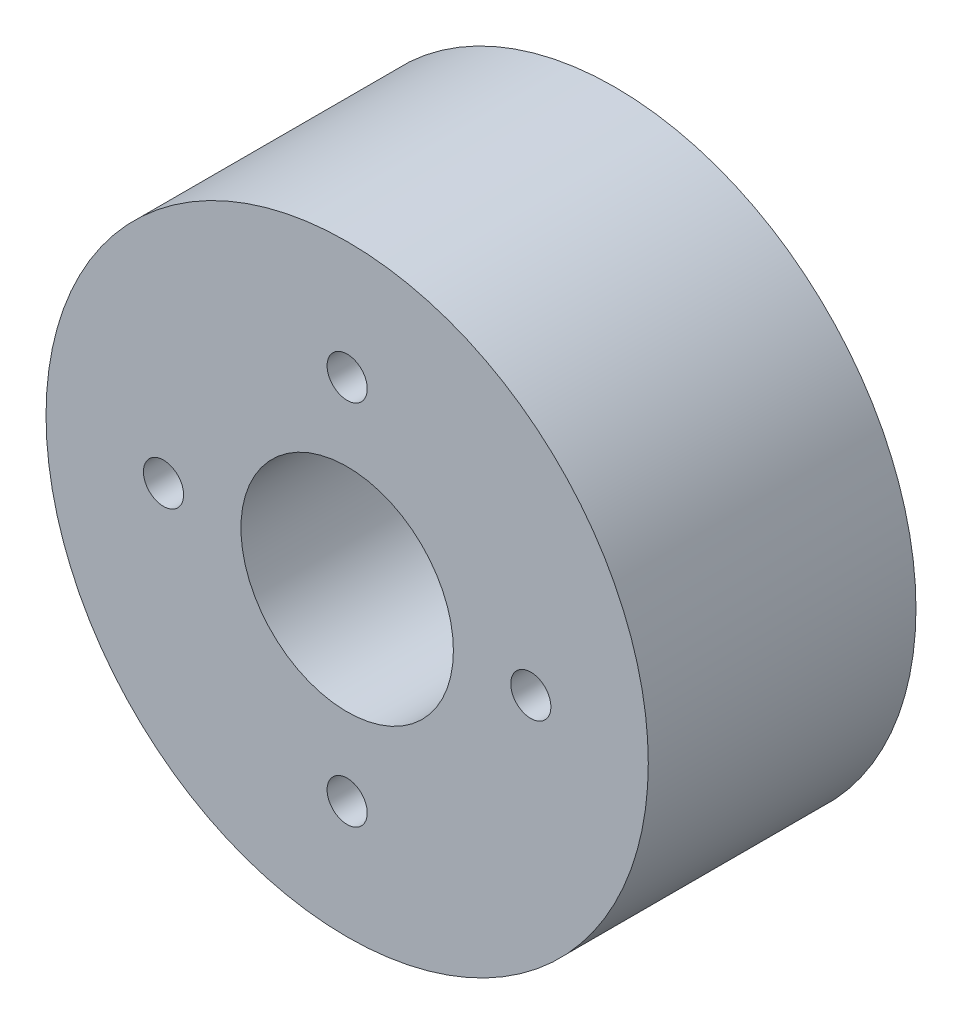
SolidWorks part; units mm, degrees
ref_plane "Front Plane" through (0, 0, 0) normal (0, 0, 1) x (1, 0, 0)
ref_plane "Top Plane" through (0, 0, 0) normal (0, 1, 0) x (1, 0, 0)
ref_plane "Right Plane" through (0, 0, 0) normal (1, 0, 0) x (0, 0, -1)
sketch "Sketch1" plane through (0, 0, 0) normal (0, 0, 1) x (1, 0, 0)
  circle A0 centre (0, 0) radius 22.5
  circle A1 centre (0, 0) radius 7.9375
  dimension "D1" = 45
  dimension "D2" = 15.875
extrude "Boss-Extrude1" add sketch "Sketch1" along normal blind 20
sketch "Sketch2" plane through (0, 0, 20) normal (0, 0, 1) x (1, 0, 0)
  circle A0 centre (0, 13.7209) radius 1.5
  circle A1 centre (13.7209, 0) radius 1.5
  circle A2 centre (0, -13.7209) radius 1.5
  circle A3 centre (-13.7209, 0) radius 1.5
  point P12 (0, 0)
  dimension "D1" = 3
  dimension "D2" = 13.7209
  dimension "D3" = 4
extrude "Cut-Extrude1" cut sketch "Sketch2" against normal through all
sketch "Sketch3" plane through (0, 0, 0) normal (0, 0, 1) x (1, 0, 0)
  circle A0 centre (0, 13.7209) radius 2.75
  circle A1 centre (13.7209, 0) radius 2.75
  circle A2 centre (0, -13.7209) radius 2.75
  circle A3 centre (-13.7209, 0) radius 2.75
  point P12 (0, 0)
  dimension "D1" = 5.5
  dimension "D2" = 4
extrude "Cut-Extrude2" cut sketch "Sketch3" along normal blind 13
